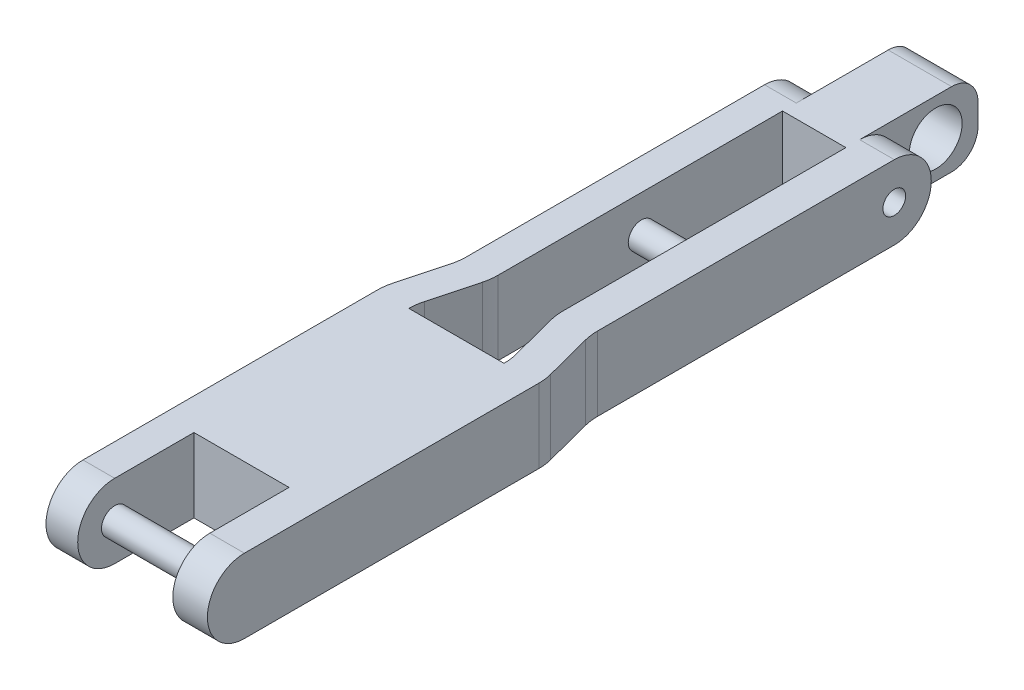
SolidWorks part; units mm, degrees
ref_plane "前视基准面" through (0, 0, 0) normal (0, 0, 1) x (1, 0, 0)
ref_plane "上视基准面" through (0, 0, 0) normal (0, 1, 0) x (1, 0, 0)
ref_plane "右视基准面" through (0, 0, 0) normal (1, 0, 0) x (0, 0, -1)
sketch "草图1" plane through (0, 0, 0) normal (0, 1, 0) x (1, 0, 0)
  line L0 (-5, 0) -> (5, 0) construction
  line L1 (5, 0) -> (5, 62.718)
  line L2 (4.6766, 65.2405) -> (2.3234, 74.2681)
  line L3 (2, 76.7906) -> (2, 140)
  line L4 (5, 0) -> (-1.5534, 0)
  line L5 (-1.5534, 0) -> (-1.5534, 62.718)
  line L6 (-1.8768, 65.2405) -> (-4.2301, 74.2681)
  line L7 (-4.5534, 76.7906) -> (-4.5534, 140)
  line L8 (-4.5534, 140) -> (2, 140)
  arc A0 (-4.2301, 74.2681) -> (-4.5534, 76.7906) centre (5.4466, 76.7906) cw
  arc A1 (2.3234, 74.2681) -> (2, 76.7906) centre (12, 76.7906) cw
  arc A2 (5, 62.718) -> (4.6766, 65.2405) centre (-5, 62.718) ccw
  arc A3 (-1.5534, 62.718) -> (-1.8768, 65.2405) centre (-11.5534, 62.718) ccw
  point P4 (0, 0)
  point P14 (-4.5534, 75.5086)
  point P17 (2, 75.5086)
  point P20 (5, 64)
  point P23 (-1.5534, 64)
  dimension "D8" = 10
  dimension "D9" = 10
  dimension "D10" = 10
  dimension "D11" = 10
  dimension "D1" = 10
  dimension "D2" = 64
  dimension "D3" = 140
  dimension "D4" = 3
  dimension "D5" = 6.5534
  dimension "D6" = 64
  dimension "D7" = 3
extrude "凸台-拉伸2" add sketch "草图1" along normal blind 14
fillet "圆角1" 2 edges at (1.7233, 14, 0) (1.7233, 0, 0) type full round first side face at (0.2233, 14, -69.8362) second side face at (0.2233, 0, -69.8362) middle face at (1.7233, 7, 0)
fillet "圆角2" 2 edges at (-1.2767, 14, -140) (-1.2767, 0, -140) type full round first side face at (0.2233, 14, -71.0029) second side face at (0.2233, 0, -71.0029) middle face at (-1.2767, 7, -140)
sketch "草图2" plane through (2, 0, 0) normal (1, 0, 0) x (0, 0, -1)
  circle A0 centre (133, 7) radius 2.15
  dimension "D1" = 4.3
extrude "切除-拉伸1" cut sketch "草图2" against normal up to next
sketch "草图4" plane through (0, 0, 0) normal (0, 1, 0) x (1, 0, 0)
  line L0 (0, 0) -> (-67.1091, 0) construction
  line L1 (-19.5534, 0) -> (-25.5534, 0)
  line L2 (-25.5534, 0) -> (-25.5534, 62.6839)
  line L3 (-25.2129, 65.2713) -> (-22.894, 73.9283)
  line L4 (-22.5534, 76.5157) -> (-22.5534, 140)
  line L5 (-22.5534, 140) -> (-16.5534, 140)
  line L6 (-16.5534, 140) -> (-16.5534, 76.5157)
  line L7 (-16.894, 73.9283) -> (-19.2129, 65.2713)
  line L8 (-19.5534, 62.6839) -> (-19.5534, 0)
  line L10 (-4.5534, 133) -> (-4.5534, 76.7906) construction
  arc A1 (-19.2129, 65.2713) -> (-19.5534, 62.6839) centre (-9.5534, 62.6839) ccw
  arc A2 (-25.5534, 62.6839) -> (-25.2129, 65.2713) centre (-15.5534, 62.6839) cw
  arc A3 (-16.5534, 76.5157) -> (-16.894, 73.9283) centre (-26.5534, 76.5157) cw
  arc A4 (-22.894, 73.9283) -> (-22.5534, 76.5157) centre (-32.5534, 76.5157) ccw
  point P16 (-19.5534, 64)
  point P19 (-25.5534, 64)
  point P22 (-16.5534, 75.1996)
  dimension "D8" = 10
  dimension "D1" = 6
  dimension "D2" = 64
  dimension "D3" = 64
  dimension "D4" = 140
  dimension "D5" = 6
  dimension "D6" = 3
  dimension "D7" = 12
extrude "凸台-拉伸3" add sketch "草图4" along normal blind 14 separate body
fillet "圆角3" 2 edges at (-19.5534, 14, -140) (-19.5534, 0, -140) type full round first side face at (-21.0534, 14, -69.7332) second side face at (-21.0534, 0, -69.7332) middle face at (-19.5534, 7, -140)
fillet "圆角4" 2 edges at (-22.5534, 0, 0) (-22.5534, 14, 0) type full round first side face at (-21.0534, 0, -68.5665) second side face at (-21.0534, 14, -68.5665) middle face at (-22.5534, 7, 0)
sketch "草图8" plane through (-19.5534, 0, 0) normal (1, 0, 0) x (0, 0, -1)
  line L0 (7, 0) -> (62.6839, 0) construction
  line L1 (62.6839, 14) -> (22, 14)
  line L2 (62.6839, 14) -> (62.6839, 0)
  line L3 (62.6839, 0) -> (22, 0)
  line L4 (22, 14) -> (22, 0)
  circle A0 centre (7, 7) radius 2.5
  dimension "D1" = 5
  dimension "D2" = 15
extrude "凸台-拉伸5" add sketch "草图8" along normal up to next
sketch "草图11" plane through (-16.5534, 0, 0) normal (1, 0, 0) x (0, 0, -1)
  circle A0 centre (103.7, 7) radius 2.5
  dimension "D2" = 5
extrude "凸台-拉伸6" add sketch "草图11" along normal up to next
sketch "草图12" plane through (-16.5534, 0, 0) normal (1, 0, 0) x (0, 0, -1)
  line L1 (130.3982, 14) -> (155.3982, 14)
  line L2 (130.3982, 14) -> (130.3982, 0)
  line L3 (130.3982, 0) -> (155.3982, 0)
  line L4 (155.3982, 14) -> (155.3982, 0)
  dimension "D1" = 25
extrude "凸台-拉伸7" add sketch "草图12" along normal blind 12
sketch "草图13" plane through (-16.5534, 0, 0) normal (-1, 0, 0) x (0, 0, 1)
  line L0 (-155.3982, 0) -> (-155.3982, 14) construction
  circle A0 centre (-147.3982, 7) radius 5
  dimension "D1" = 10
  dimension "D2" = 8
extrude "切除-拉伸2" cut sketch "草图13" against normal blind 12
fillet "圆角5" radius 5 2 edges at (-10.5534, 14, -155.3982) (-10.5534, 0, -155.3982)
